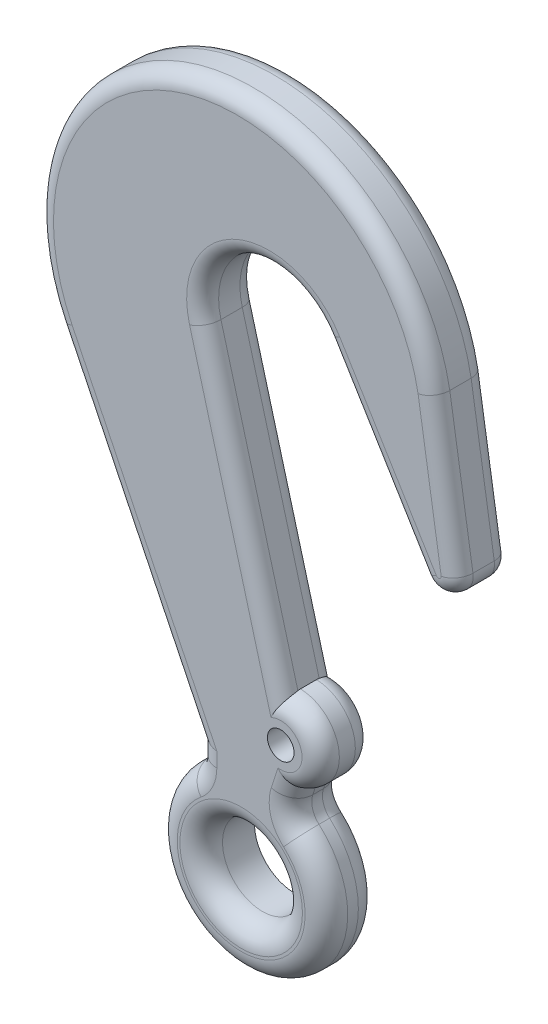
SolidWorks part; units mm, degrees
ref_plane "Front Plane" through (0, 0, 0) normal (0, 0, 1) x (1, 0, 0)
ref_plane "Top Plane" through (0, 0, 0) normal (0, 1, 0) x (1, 0, 0)
ref_plane "Right Plane" through (0, 0, 0) normal (1, 0, 0) x (0, 0, -1)
sketch "Sketch1" plane through (0, 0, 0) normal (0, 0, 1) x (1, 0, 0)
  line L0 (9.309, -75.606) -> (-7.8367, -75.606) construction
  line L1 (71.6923, 37.5) -> (-71.6923, 37.5) construction
  line L2 (36.9004, 6.679) -> (44, -38.321)
  line L3 (16.6732, 6.5064) -> (44, -38.321)
  line L4 (-33.7038, -16.4409) -> (-7.8367, -69.4682)
  line L5 (-6.0621, -3.2797) -> (8.3687, -56.3528)
  line L6 (-7.8367, -69.4682) -> (-7.8367, -75.606)
  line L9 (9.309, -75.606) -> (10.8541, -70.8507)
  arc A0 (37.1644, 5.0061) -> (-33.7038, -16.4409) centre (0, 0) ccw
  arc A1 (16.6732, 6.5064) -> (-6.0621, -3.2797) centre (6, 0) ccw
  arc A2 (10.8541, -70.8507) -> (8.3687, -56.3528) centre (8.1633, -63.85) ccw
  circle A9 centre (8.1633, -63.85) radius 2.5
  circle A10 centre (0.7361, -89.1155) radius 7.5
  circle A11 centre (0.7361, -89.1155) radius 16
  point P7 (0, 37.5)
  point P14 (0, 0)
  point P15 (0, 0)
  point P16 (0, 0)
  point P17 (10.8541, -70.8507)
  point P24 (0, 0)
  dimension "D3" = 75
  dimension "D4" = 15
  dimension "D6" = 32
  dimension "D9" = 18
  dimension "D11" = 55
  dimension "D5" = 12.5
  dimension "D16" = 59
  dimension "D28" = 5
  dimension "D8" = 15
  dimension "D7" = 5
  dimension "D12" = 45
  dimension "D13" = 52.5
  dimension "D14" = 44
  dimension "D15" = 37.5
  dimension "D19" = 6
  dimension "D20" = 38
  dimension "D21" = 63.85
  dimension "D22" = 16
extrude "Boss-Extrude1" add sketch "Sketch1" along normal blind 10 contours L9 A2 L5 A1 L3 L2 A0 L4 L6 | A11 | A10 region at (35.6553, 5.6253, 0)
fillet "Fillet1" radius 3.5 1 edges at (44, -38.321, 5)
fillet "Fillet6" radius 3 14 edges at (-11.6699, 35.6379, 0) (-11.6699, 35.6379, 10) (39.0729, -7.0912, 0) (38.9948, -24.6923, 0) (25.7364, -8.3611, 0) (1.0579, 11.4815, 0) (39.0729, -7.0912, 10) (38.9948, -24.6923, 10) (25.7364, -8.3611, 10) (1.0579, 11.4815, 10) (-20.7703, -42.9546, 0) (-20.7703, -42.9546, 10) (1.1533, -29.8163, 0) (1.1533, -29.8163, 10)
fillet "Fillet7" radius 4 9 edges at (-7.8367, -69.1158, 10) (-7.8367, -69.1158, 0) (10.0815, -73.2283, 10) (10.0815, -73.2283, 0) (8.2361, -89.1155, 10) (-7.8367, -75.606, 5) (0.7361, -105.1155, 10) (9.309, -75.606, 5) (0.7361, -105.1155, 0)
fillet "Fillet8" radius 3.5 2 edges at (15.6395, -63.2532, 0) (15.6395, -63.2532, 10)
